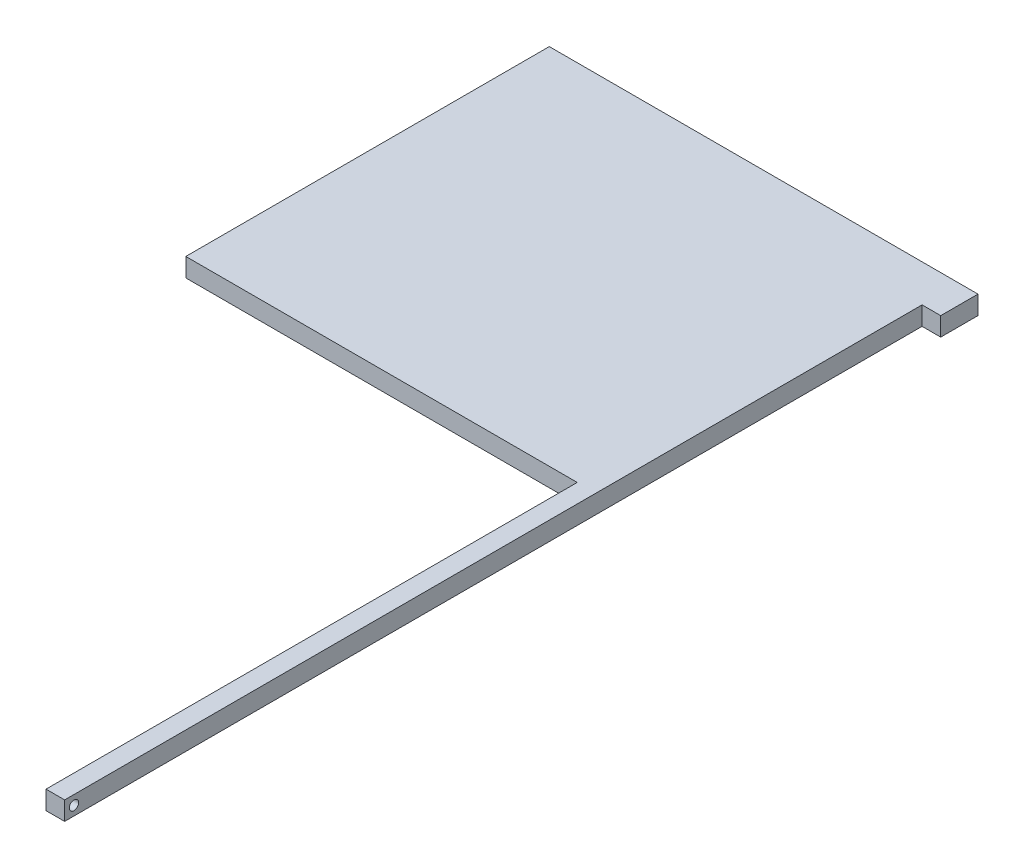
SolidWorks part; units mm, degrees
other "Markup1"
sketch "Sketch12" plane through (250.825, 22.225, 158.75) normal (0.1153, 0.0728, 0.9907) x (0.9687, -0.2289, -0.0959)
material "6061 Alloy"
ref_plane "Front Plane" through (0, 0, 0) normal (0, 0, 1) x (1, 0, 0)
ref_plane "Top Plane" through (0, 0, 0) normal (0, 1, 0) x (1, 0, 0)
ref_plane "Right Plane" through (0, 0, 0) normal (1, 0, 0) x (0, 0, -1)
sketch "Sketch1" plane through (0, 0, 0) normal (0, 1, 0) x (1, 0, 0)
  line L1 (-241.3, 152.4) -> (241.3, 152.4)
  line L2 (-241.3, 152.4) -> (-241.3, -152.4)
  line L3 (-241.3, -152.4) -> (241.3, -152.4)
  line L4 (241.3, 152.4) -> (241.3, -152.4)
  line L5 (-241.3, 152.4) -> (241.3, -152.4) construction
  line L6 (-241.3, -152.4) -> (241.3, 152.4) construction
  point P0 (0, 0)
  dimension "D1" = 482.6
  dimension "D2" = 304.8
extrude "Boss-Extrude1" add sketch "Sketch1" along normal blind 12.7
sketch "Sketch2" plane through (0, 12.7, 0) normal (0, 1, 0) x (1, 0, 0)
  line L0 (-241.3, -152.4) -> (241.3, -152.4) construction
  line L1 (-241.3, 152.4) -> (-234.95, 152.4)
  line L2 (-241.3, 152.4) -> (-241.3, -152.4)
  line L3 (-241.3, -152.4) -> (-234.95, -152.4)
  line L4 (-234.95, 28.575) -> (-234.95, -152.4)
  line L5 (241.3, 152.4) -> (-241.3, 152.4) construction
  line L6 (241.3, 152.4) -> (234.95, 152.4)
  line L7 (241.3, 152.4) -> (241.3, -152.4)
  line L8 (241.3, -152.4) -> (234.95, -152.4)
  line L9 (234.95, 28.575) -> (234.95, -152.4)
  line L10 (-234.95, 152.4) -> (234.95, 152.4)
  line L12 (-234.95, 28.575) -> (234.95, 28.575)
  point P14 (-238.125, -152.4)
  dimension "D1" = 6.35
  dimension "D2" = 180.975
extrude "Boss-Extrude2" add sketch "Sketch2" along normal blind 6.35
sketch "Sketch3" plane through (-241.3, 0, 0) normal (-1, 0, 0) x (0, 0, 1)
  line L0 (152.4, 19.05) -> (152.4, 0) construction
  line L1 (-152.4, 19.05) -> (152.4, 19.05) construction
  circle A0 centre (149.225, 15.875) radius 1.5875
  dimension "D3" = 3.175
  dimension "D1" = 3.175
  dimension "D2" = 3.175
extrude "Cut-Extrude1" cut sketch "Sketch3" against normal through all
sketch "Sketch4" plane through (0, 0, 152.4) normal (0, 0, 1) x (1, 0, 0)
  line L0 (-241.3, 19.05) -> (-241.3, 0) construction
  line L1 (-241.3, 12.7) -> (-247.65, 12.7)
  line L2 (-241.3, 12.7) -> (-241.3, 0)
  line L3 (-241.3, 0) -> (-247.65, 0)
  line L4 (-247.65, 12.7) -> (-247.65, 0)
  line L5 (-241.3, 0) -> (241.3, 0) construction
  dimension "D1" = 12.7
  dimension "D2" = 6.35
extrude "Boss-Extrude3" add sketch "Sketch4" against normal blind 292.1
sketch "Sketch5" plane through (-241.3, 0, 0) normal (-1, 0, 0) x (0, 0, 1)
  line L0 (-152.4, 0) -> (-139.7, 0) construction
  line L1 (-152.4, 19.05) -> (-139.7, 19.05)
  line L2 (-152.4, 19.05) -> (-152.4, 0)
  line L3 (-152.4, 0) -> (-139.7, 0)
  line L4 (-139.7, 19.05) -> (-139.7, 0)
  line L5 (-139.7, 0) -> (-139.7, 12.7) construction
extrude "Boss-Extrude4" add sketch "Sketch5" along normal up to surface (6.35 mm away) up to face at (-247.65, 6.35, 6.35)
mirror "Mirror1" about plane through (0, 0, 0) normal (1, 0, 0) of "Boss-Extrude4", "Boss-Extrude3"
sketch "Sketch6" plane through (-241.3, 0, 0) normal (-1, 0, 0) x (0, 0, 1)
  line L0 (147.32, 6.35) -> (128.27, 6.35) construction
  line L1 (147.32, 2.54) -> (128.27, 2.54)
  line L2 (147.32, 10.16) -> (128.27, 10.16)
  line L3 (152.4, 19.05) -> (152.4, 12.7) construction
  line L5 (152.4, 12.7) -> (152.4, 0) construction
  arc A0 (147.32, 2.54) -> (147.32, 10.16) centre (147.32, 6.35) ccw
  arc A1 (128.27, 10.16) -> (128.27, 2.54) centre (128.27, 6.35) ccw
  point P2 (137.795, 6.35)
  point P11 (152.4, 6.35)
  dimension "D1" = 19.05
  dimension "D2" = 5.08
  dimension "D3" = 7.62
extrude "Cut-Extrude2" cut sketch "Sketch6" against normal blind 25.4 from surface starting at face at (-247.65, 10.5833, -46.5667)
extrude "Cut-Extrude3" cut sketch "Sketch6<2>" along normal blind 25.4 from surface starting at face at (247.65, 10.5833, -46.5667)
sketch "Sketch6<2>" plane through (-241.3, 0, 0) normal (-1, 0, 0) x (0, 0, 1) same geometry as "Sketch6"
sketch "Sketch11" plane through (0, 0, 0) normal (0, -1, 0) x (1, 0, 0)
  line L0 (-247.65, 124.46) -> (-222.25, 124.46)
  line L1 (-222.25, 124.46) -> (-222.25, 140.97)
  line L2 (-222.25, 140.97) -> (-247.65, 124.46)
  line L3 (-222.25, 128.27) -> (-222.25, 147.32) construction
  dimension "D1" = 10.16
extrude "Boss-Extrude5" add sketch "Sketch11" against normal up to surface (10.16 mm away) from surface up to face at (-234.95, 10.16, 137.795) starting at face at (-234.95, 2.54, 137.795)
mirror "Mirror2" about plane through (0, 0, 0) normal (1, 0, 0) of "Boss-Extrude5"
ref_plane "Plane1" through (247.65, 19.05, -152.4) normal (-1, 0, 0) x (0, 0, 1)
sketch "Sketch13" plane through (247.65, 19.05, -152.4) normal (-1, 0, 0) x (0, 0, 1)
  line L0 (0, 0) -> (0, -19.05) construction
  line L1 (304.8, -19.05) -> (0, -19.05)
  line L2 (304.8, -19.05) -> (304.8, -6.35)
  line L3 (304.8, -6.35) -> (0, -6.35)
  line L4 (0, -19.05) -> (0, -6.35)
  line L5 (12.7, -6.35) -> (304.8, -6.35) construction
extrude "Cut-Extrude5" cut sketch "Sketch13" against normal through all and the other way through all
sketch "Sketch14" plane through (0, 19.05, 0) normal (0, 1, 0) x (1, 0, 0)
  line L0 (-101.6, 152.4) -> (-101.6, 28.575)
  line L1 (247.65, 152.4) -> (-247.65, 152.4) construction
  line L2 (-234.95, 28.575) -> (234.95, 28.575) construction
  line L3 (101.6, 28.575) -> (101.6, 152.4)
  line L4 (-247.65, 139.7) -> (-247.65, 152.4) construction
  line L5 (247.65, 139.7) -> (247.65, 152.4) construction
  dimension "D1" = 146.05
  dimension "D2" = 146.05
sketch "Sketch15" [suppressed] plane through (0, 19.05, 0) normal (0, 1, 0) x (1, 0, 0)
  line L1 (-101.6, 152.4) -> (280.6914, 152.4)
  line L2 (-101.6, 152.4) -> (-101.6, -175.8205)
  line L3 (-101.6, -175.8205) -> (280.6914, -175.8205)
  line L4 (280.6914, 152.4) -> (280.6914, -175.8205)
extrude "Cut-Extrude6" [suppressed] cut sketch "Sketch15" against normal through all
sketch "Sketch16" [suppressed] plane through (0, 19.05, 0) normal (0, 1, 0) x (1, 0, 0)
  line L1 (-101.6, 152.4) -> (-271.3696, 152.4)
  line L2 (-101.6, 152.4) -> (-101.6, -163.9093)
  line L3 (-101.6, -163.9093) -> (-271.3696, -163.9093)
  line L4 (-271.3696, 152.4) -> (-271.3696, -163.9093)
  line L5 (101.6, 152.4) -> (270.8517, 152.4)
  line L6 (101.6, 152.4) -> (101.6, -183.0709)
  line L7 (101.6, -183.0709) -> (270.8517, -183.0709)
  line L8 (270.8517, 152.4) -> (270.8517, -183.0709)
extrude "Cut-Extrude7" [suppressed] cut sketch "Sketch16" against normal through all
sketch "Sketch17" plane through (0, 19.05, 0) normal (0, 1, 0) x (1, 0, 0)
  line L1 (101.6, 152.4) -> (-283.7987, 152.4)
  line L2 (101.6, 152.4) -> (101.6, -172.1954)
  line L3 (101.6, -172.1954) -> (-283.7987, -172.1954)
  line L4 (-283.7987, 152.4) -> (-283.7987, -172.1954)
extrude "Cut-Extrude8" cut sketch "Sketch17" against normal through all
